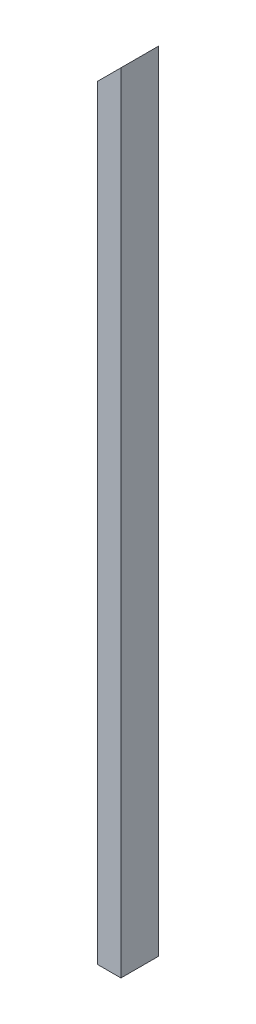
SolidWorks part; units mm, degrees
material "1023 Carbon Steel Sheet (SS)"
ref_plane "Front Plane" through (0, 0, 0) normal (0, 0, 1) x (1, 0, 0)
ref_plane "Top Plane" through (0, 0, 0) normal (0, 1, 0) x (1, 0, 0)
ref_plane "Right Plane" through (0, 0, 0) normal (1, 0, 0) x (0, 0, -1)
sketch "Sketch3" plane through (0, 0, 0) normal (0, 0, 1) x (1, 0, 0)
  line L0 (0, 0) -> (0, 2057.4)
  line L1 (0, 2057.4) -> (63.5, 2120.9)
  line L2 (63.5, 0) -> (63.5, 2120.9)
  line L3 (63.5, 0) -> (0, 0)
  dimension "D1" = 2057.4
  dimension "D2" = 63.5
  dimension "D3" = 135
extrude "Boss-Extrude1" add sketch "Sketch3" along normal blind 101.6
